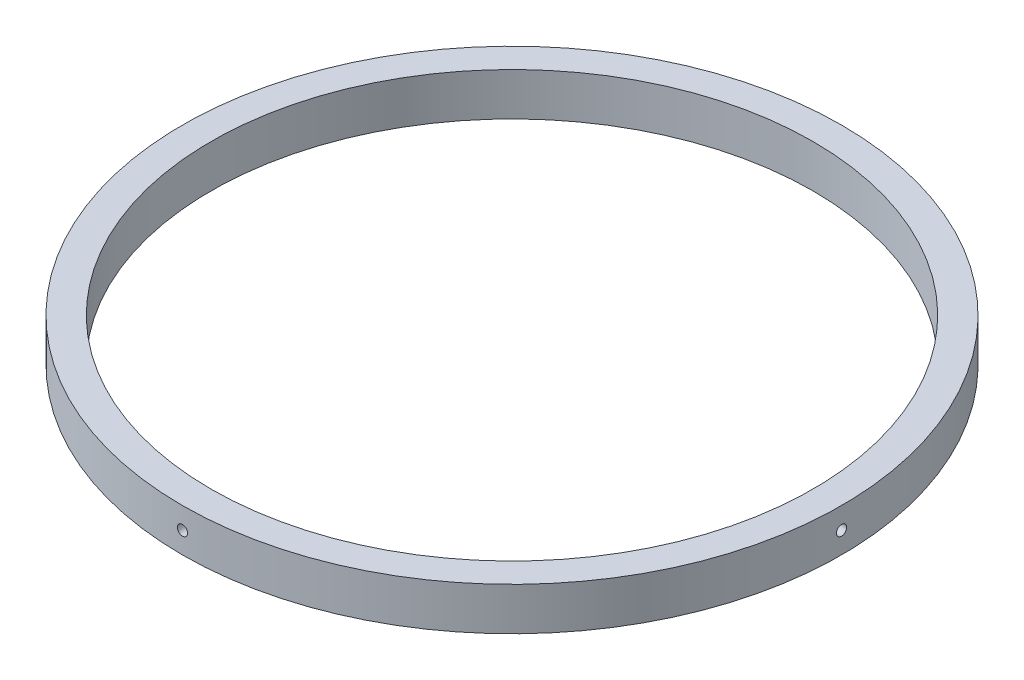
SolidWorks part; units mm, degrees
ref_plane "Front Plane" through (0, 0, 0) normal (0, 0, 1) x (1, 0, 0)
ref_plane "Top Plane" through (0, 0, 0) normal (0, 1, 0) x (1, 0, 0)
ref_plane "Right Plane" through (0, 0, 0) normal (1, 0, 0) x (0, 0, -1)
sketch "Sketch1" plane through (0, 0, 0) normal (0, 1, 0) x (1, 0, 0)
  circle A0 centre (0, 0) radius 73.3171
  circle A1 centre (0, 0) radius 66.9671
  dimension "D1" = 146.6342
  dimension "D2" = 133.9342
extrude "Boss-Extrude1" add sketch "Sketch1" along normal blind 9.525
ref_plane "Plane1" through (0, 0, 73.3171) normal (0, 0, 1) x (1, 0, 0)
sketch "Sketch2" plane through (0, 0, 73.3171) normal (0, 0, 1) x (1, 0, 0)
  line L0 (0, 0) -> (0, 9.525) construction
  line L1 (73.3171, 9.525) -> (-73.3171, 9.525) construction
  point P5 (0, 4.7625)
hole_wizard "Tap Drill for #4-40 Tap1" positions "Sketch2" profile "Sketch3" hole size "#4-40" standard "ANSI Inch"
sketch "Sketch3" plane through (0, 4.7625, 73.3171) normal (1, 0, 0) x (0, -1, 0)
  line L0 (0, 0) -> (0, 5.4417)
  line L1 (0, 5.4417) -> (1.1303, 4.7625)
  line L2 (1.1303, 4.7625) -> (1.1303, 0)
  line L5 (1.1303, 0) -> (0, 0)
  line L10 (0, 5.4417) -> (-1.1303, 4.7625) construction
  line L11 (0, -6.35) -> (0, 107.95) construction
  dimension "Hole Dia." = 2.2606
  dimension "Hole Depth" = 4.7625
  dimension "Drill Angle" = 118
pattern_circular "CirPattern1" count 4 every 90 about axis through (0, 9.525, 0) along (0, 1, 0) of "Tap Drill for #4-40 Tap1"
equation "\"OD\"= 5.773"
equation "\"ID\"= \"OD\" - 0.5"
equation "\"thk\"= 3 / 8"
equation "\"D1@Sketch1\"=\"OD\""
equation "\"D2@Sketch1\"=\"ID\""
equation "\"D1@Boss-Extrude1\"=\"thk\""
